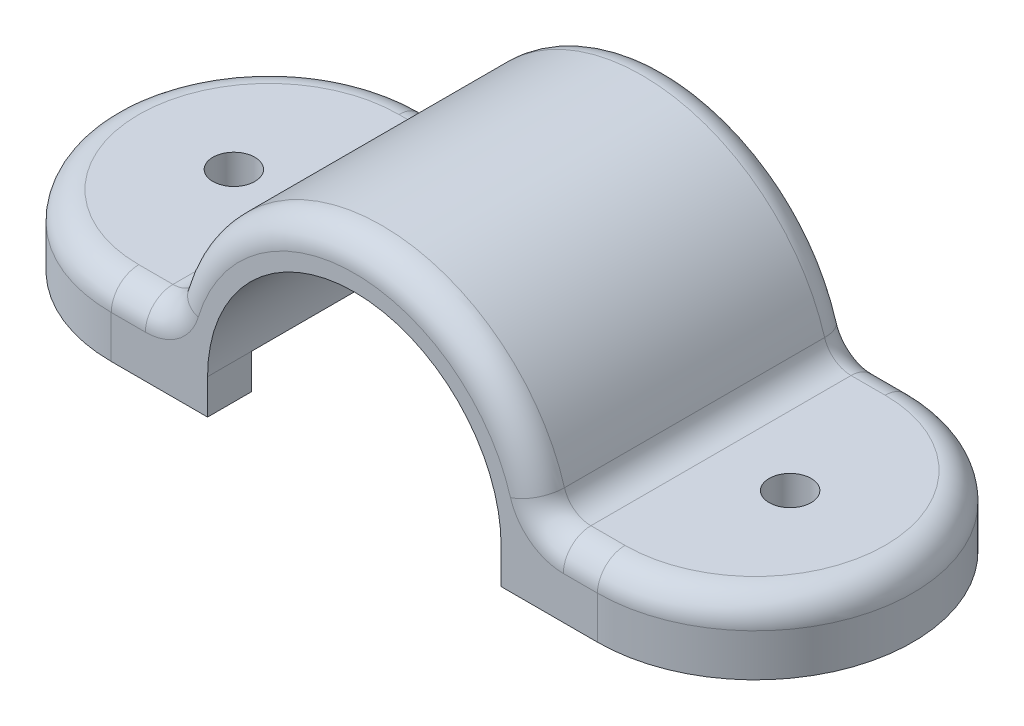
SolidWorks part; units mm, degrees
ref_plane "Front Plane" through (0, 0, 0) normal (0, 0, 1) x (1, 0, 0)
ref_plane "Top Plane" through (0, 0, 0) normal (0, 1, 0) x (1, 0, 0)
ref_plane "Right Plane" through (0, 0, 0) normal (1, 0, 0) x (0, 0, -1)
sketch "Sketch1" plane through (0, 0, 0) normal (0, 0, 1) x (1, 0, 0)
  line L0 (-13.8176, 0) -> (13.8176, 0) construction
  line L1 (0, 10.6426) -> (0, 13.8176) construction
  line L2 (-10.6426, 0) -> (-13.8176, 0)
  line L6 (10.6426, 0) -> (13.8176, 0)
  circle A0 centre (0, 0) radius 10.6426
  circle A1 centre (0, 0) radius 13.8176
  point P6 (-10.6426, 0)
  point P7 (10.6426, 0)
  dimension "D1" = 21.2852
  dimension "D2" = 3.175
extrude "Boss-Extrude1" add sketch "Sketch1" along normal blind 22.86 contours A1 | A1 | L6 A1 L2 A0 region at (-12.2301, 0.309, 0)
sketch "Sketch9" plane through (0, 0, 0) normal (0, -1, 0) x (1, 0, 0)
  line L1 (-13.8176, 0) -> (-10.6426, 0)
  line L2 (-13.8176, 0) -> (-13.8176, 22.86)
  line L3 (-13.8176, 22.86) -> (-10.6426, 22.86)
  line L4 (-10.6426, 0) -> (-10.6426, 22.86)
extrude "Boss-Extrude8" add sketch "Sketch9" against normal blind 2.54 and the other way blind 2.54
sketch "Sketch10" plane through (0, 0, 0) normal (0, -1, 0) x (1, 0, 0)
  line L1 (10.6426, 22.86) -> (13.8176, 22.86)
  line L2 (10.6426, 22.86) -> (10.6426, 0)
  line L3 (10.6426, 0) -> (13.8176, 0)
  line L4 (13.8176, 22.86) -> (13.8176, 0)
extrude "Boss-Extrude9" add sketch "Sketch10" against normal blind 2.54 and the other way blind 2.54
sketch "Sketch11" plane through (-13.8176, 0, 0) normal (-1, 0, 0) x (0, 0, 1)
  line L3 (0, 2.54) -> (0, 0)
  line L4 (3.175, 0) -> (19.685, 0)
  line L6 (0, 2.54) -> (22.86, 2.54)
  line L7 (0, 2.54) -> (0, -2.54)
  line L8 (0, -2.54) -> (3.175, -2.54)
  line L9 (3.175, 0) -> (3.175, -2.54)
  line L12 (22.86, -2.54) -> (19.685, -2.54)
  line L13 (19.685, 0) -> (19.685, -2.54)
  line L14 (22.86, 2.54) -> (22.86, -2.54)
  line M2 (22.86, -2.54) -> (22.86, 2.54)
  line M3 (22.86, 2.54) -> (0, 2.54)
  line M4 (0, 2.54) -> (0, -2.54)
  line M24 (0, -2.54) -> (22.86, -2.54)
  dimension "D1" = 3.175
  dimension "D2" = 3.175
extrude "Boss-Extrude10" add sketch "Sketch11" along normal blind 3.81 contours L4 L13 L9 M24 M2 M3 M4 region at (-13.8176, 0.7178, 11.43)
sketch "Sketch19" plane through (13.8176, 0, 0) normal (1, 0, 0) x (0, 0, -1)
  line L10 (-19.685, 0) -> (-3.175, 0)
  line L11 (-19.685, -2.54) -> (-19.685, 0)
  line L12 (-22.86, -2.54) -> (-19.685, -2.54)
  line L13 (-22.86, 2.54) -> (-22.86, -2.54)
  line L14 (0, 2.54) -> (-22.86, 2.54)
  line L15 (0, -2.54) -> (0, 2.54)
  line L16 (-3.175, -2.54) -> (0, -2.54)
  line L17 (-3.175, 0) -> (-3.175, -2.54)
  line L18 (-19.685, 0) -> (-3.175, 0)
  line L19 (-19.685, -2.54) -> (-19.685, 0)
  line L20 (-22.86, -2.54) -> (-19.685, -2.54)
  line L21 (-22.86, 2.54) -> (-22.86, -2.54)
  line L22 (0, 2.54) -> (-22.86, 2.54)
  line L23 (0, -2.54) -> (0, 2.54)
  line L24 (-3.175, -2.54) -> (0, -2.54)
  line L25 (-3.175, 0) -> (-3.175, -2.54)
  dimension "D1" = 0
extrude "Boss-Extrude11" add sketch "Sketch19" along normal blind 3.81 contours L22 L21 L20 L19 L18 L25 L24 L23
sketch "Sketch20" plane through (-17.6276, 0, 0) normal (-1, 0, 0) x (0, 0, 1)
  line L0 (11.43, 2.54) -> (11.43, 0)
  line L1 (0, 2.54) -> (22.86, 2.54) construction
  line L2 (3.175, 0) -> (19.685, 0) construction
  line L3 (11.43, 0) -> (19.685, 0)
  line L4 (19.685, 0) -> (19.685, -2.54)
  line L5 (19.685, -2.54) -> (22.86, -2.54)
  line L6 (22.86, -2.54) -> (22.86, 2.54)
  line L7 (22.86, 2.54) -> (11.43, 2.54)
revolve "Revolve1" add sketch "Sketch20" angle 180 about L0
sketch "Sketch21" plane through (17.6276, 0, 0) normal (1, 0, 0) x (0, 0, -1)
  line L0 (-11.43, 2.54) -> (-11.43, 0)
  line L1 (0, 2.54) -> (-22.86, 2.54) construction
  line L3 (-11.43, 0) -> (-3.175, 0)
  line L4 (-3.175, 0) -> (-3.175, -2.54)
  line L5 (-3.175, -2.54) -> (0, -2.54)
  line L6 (0, -2.54) -> (0, 2.54)
  line L7 (0, 2.54) -> (-11.43, 2.54)
revolve "Revolve2" add sketch "Sketch21" angle 180 about L0
sketch "Sketch22" plane through (-13.8176, 0, 0) normal (-1, 0, 0) x (0, 0, 1)
  line L4 (19.685, 0) -> (3.175, 0)
  line L5 (3.175, 0) -> (3.175, -2.54)
  line L6 (3.175, -2.54) -> (19.685, -2.54)
  line L7 (19.685, -2.54) -> (19.685, 0)
  line L8 (19.685, 0) -> (3.175, 0)
  line L9 (3.175, 0) -> (3.175, -2.54)
  line L10 (3.175, -2.54) -> (19.685, -2.54)
  line L11 (19.685, -2.54) -> (19.685, 0)
  dimension "D1" = 0
extrude "Cut-Extrude1" cut sketch "Sketch22" against normal blind 3.81
sketch "Sketch23" plane through (13.8176, 0, 0) normal (1, 0, 0) x (0, 0, -1)
  line L4 (-3.175, -2.54) -> (-3.175, 0)
  line L5 (-3.175, 0) -> (-19.685, 0)
  line L6 (-19.685, 0) -> (-19.685, -2.54)
  line L7 (-19.685, -2.54) -> (-3.175, -2.54)
  line L8 (-3.175, -2.54) -> (-3.175, 0)
  line L9 (-3.175, 0) -> (-19.685, 0)
  line L10 (-19.685, 0) -> (-19.685, -2.54)
  line L11 (-19.685, -2.54) -> (-3.175, -2.54)
  dimension "D1" = 0
extrude "Cut-Extrude2" cut sketch "Sketch23" against normal blind 3.81
sketch "Sketch24" plane through (0, 2.54, 0) normal (0, 1, 0) x (1, 0, 0)
  line L0 (-17.6276, -11.43) -> (-20.1676, -11.43)
  line L1 (-13.5821, -22.86) -> (-17.6276, -22.86)
  line L2 (-13.5821, -22.86) -> (-13.5821, 0)
  line L3 (-13.5821, 0) -> (-17.6276, 0)
  line L4 (-17.6276, -22.86) -> (-17.6276, 0)
  line L5 (13.5821, -22.86) -> (17.6276, -22.86)
  line L6 (13.5821, -22.86) -> (13.5821, 0)
  line L7 (13.5821, 0) -> (17.6276, 0)
  line L8 (17.6276, -22.86) -> (17.6276, 0)
  line L9 (17.6276, -11.43) -> (20.1676, -11.43)
  circle A0 centre (-17.6276, -11.43) radius 8.255
  circle A1 centre (17.6276, -11.43) radius 8.255
  circle A2 centre (-20.1676, -11.43) radius 1.524
  circle A3 centre (20.1676, -11.43) radius 1.524
  dimension "D1" = 16.51
  dimension "D3" = 3.048
  dimension "D2" = 2.54
extrude "Cut-Extrude3" cut sketch "Sketch24" against normal blind 3.81 contours A2 | A3 region at (-21.6485, 2.54, 11.43) region at (20.1676, 2.54, 9.9491)
fillet "Fillet1" radius 2 10 edges at (0, 13.8176, 0) (0, 13.8176, 22.86) (15.6049, 2.54, 22.86) (15.6049, 2.54, 0) (-15.6049, 2.54, 0) (-15.6049, 2.54, 22.86) (13.5821, 2.54, 11.43) (-13.5821, 2.54, 11.43) (29.0576, 2.54, 11.43) (-29.0576, 2.54, 11.43)
